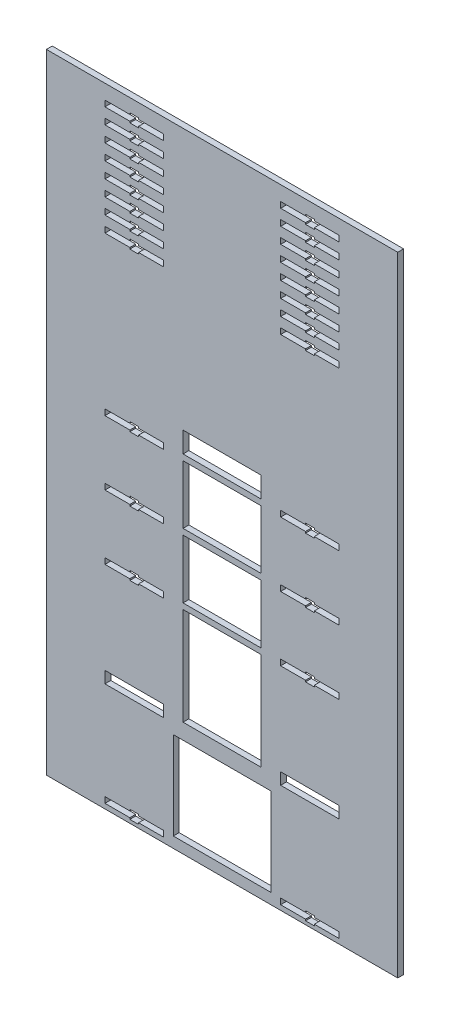
SolidWorks part; units mm, degrees
ref_plane "Front Plane" through (0, 0, 0) normal (0, 0, 1) x (1, 0, 0)
ref_plane "Top Plane" through (0, 0, 0) normal (0, 1, 0) x (1, 0, 0)
ref_plane "Right Plane" through (0, 0, 0) normal (1, 0, 0) x (0, 0, -1)
sketch "Sketch1" plane through (0, 0, 0) normal (0, 0, 1) x (1, 0, 0)
  line L0 (180, -180) -> (0, -180)
  line L1 (0, -180) -> (0, 142)
  line L2 (180, 142) -> (180, -180)
  line L3 (0, 142) -> (180, 142)
  line L4 (30, -174.5) -> (30, -177.5)
  line L5 (42.75, -174.5) -> (30, -174.5)
  line L6 (30, -177.5) -> (42.75, -177.5)
  line L7 (42.75, -173.75) -> (42.75, -174.5)
  line L8 (42.75, -177.5) -> (42.75, -178.25)
  line L9 (47.25, -173.75) -> (42.75, -173.75)
  line L10 (42.75, -178.25) -> (47.25, -178.25)
  line L11 (47.25, -174.5) -> (47.25, -173.75)
  line L12 (47.25, -178.25) -> (47.25, -177.5)
  line L13 (60, -174.5) -> (47.25, -174.5)
  line L14 (47.25, -177.5) -> (60, -177.5)
  line L15 (60, -177.5) -> (60, -174.5)
  line L16 (30, -121.5) -> (30, -124.5)
  line L17 (42.75, -121.5) -> (30, -121.5)
  line L18 (30, -124.5) -> (42.75, -124.5)
  line L19 (42.75, -120.75) -> (42.75, -121.5)
  line L20 (42.75, -124.5) -> (42.75, -125.25)
  line L21 (47.25, -120.75) -> (42.75, -120.75)
  line L22 (42.75, -125.25) -> (47.25, -125.25)
  line L23 (47.25, -121.5) -> (47.25, -120.75)
  line L24 (47.25, -125.25) -> (47.25, -124.5)
  line L25 (60, -121.5) -> (47.25, -121.5)
  line L26 (47.25, -124.5) -> (60, -124.5)
  line L27 (60, -124.5) -> (60, -121.5)
  line L28 (30, -68.5) -> (30, -71.5)
  line L29 (42.75, -68.5) -> (30, -68.5)
  line L30 (30, -71.5) -> (42.75, -71.5)
  line L31 (42.75, -67.75) -> (42.75, -68.5)
  line L32 (42.75, -71.5) -> (42.75, -72.25)
  line L33 (47.25, -67.75) -> (42.75, -67.75)
  line L34 (42.75, -72.25) -> (47.25, -72.25)
  line L35 (47.25, -68.5) -> (47.25, -67.75)
  line L36 (47.25, -72.25) -> (47.25, -71.5)
  line L37 (60, -68.5) -> (47.25, -68.5)
  line L38 (47.25, -71.5) -> (60, -71.5)
  line L39 (60, -71.5) -> (60, -68.5)
  line L40 (30, -35.5) -> (30, -38.5)
  line L41 (42.75, -35.5) -> (30, -35.5)
  line L42 (30, -38.5) -> (42.75, -38.5)
  line L43 (42.75, -34.75) -> (42.75, -35.5)
  line L44 (42.75, -38.5) -> (42.75, -39.25)
  line L45 (47.25, -34.75) -> (42.75, -34.75)
  line L46 (42.75, -39.25) -> (47.25, -39.25)
  line L47 (47.25, -35.5) -> (47.25, -34.75)
  line L48 (47.25, -39.25) -> (47.25, -38.5)
  line L49 (60, -35.5) -> (47.25, -35.5)
  line L50 (47.25, -38.5) -> (60, -38.5)
  line L51 (60, -38.5) -> (60, -35.5)
  line L52 (110, -5.5) -> (70, -5.5)
  line L53 (70, -5.5) -> (70, -135.5)
  line L54 (110, -135.5) -> (110, -5.5)
  line L55 (70, -135.5) -> (110, -135.5)
  line L56 (72.5, -174.5) -> (107.5, -174.5)
  line L57 (72.5, -147.5) -> (72.5, -174.5)
  line L58 (107.5, -174.5) -> (107.5, -147.5)
  line L59 (107.5, -147.5) -> (72.5, -147.5)
  line L60 (120, -174.5) -> (120, -177.5)
  line L61 (132.75, -174.5) -> (120, -174.5)
  line L62 (120, -177.5) -> (132.75, -177.5)
  line L63 (132.75, -173.75) -> (132.75, -174.5)
  line L64 (132.75, -177.5) -> (132.75, -178.25)
  line L65 (137.25, -173.75) -> (132.75, -173.75)
  line L66 (132.75, -178.25) -> (137.25, -178.25)
  line L67 (137.25, -174.5) -> (137.25, -173.75)
  line L68 (137.25, -178.25) -> (137.25, -177.5)
  line L69 (150, -174.5) -> (137.25, -174.5)
  line L70 (137.25, -177.5) -> (150, -177.5)
  line L71 (150, -177.5) -> (150, -174.5)
  line L72 (150, -121.5) -> (137.25, -121.5)
  line L73 (150, -124.5) -> (150, -121.5)
  line L74 (137.25, -121.5) -> (137.25, -120.75)
  line L75 (137.25, -124.5) -> (150, -124.5)
  line L76 (137.25, -120.75) -> (132.75, -120.75)
  line L77 (137.25, -125.25) -> (137.25, -124.5)
  line L78 (132.75, -120.75) -> (132.75, -121.5)
  line L79 (132.75, -125.25) -> (137.25, -125.25)
  line L80 (132.75, -121.5) -> (120, -121.5)
  line L81 (132.75, -124.5) -> (132.75, -125.25)
  line L82 (120, -121.5) -> (120, -124.5)
  line L83 (120, -124.5) -> (132.75, -124.5)
  line L84 (150, -68.5) -> (137.25, -68.5)
  line L85 (150, -71.5) -> (150, -68.5)
  line L86 (137.25, -68.5) -> (137.25, -67.75)
  line L87 (137.25, -71.5) -> (150, -71.5)
  line L88 (137.25, -67.75) -> (132.75, -67.75)
  line L89 (137.25, -72.25) -> (137.25, -71.5)
  line L90 (132.75, -67.75) -> (132.75, -68.5)
  line L91 (132.75, -72.25) -> (137.25, -72.25)
  line L92 (132.75, -68.5) -> (120, -68.5)
  line L93 (132.75, -71.5) -> (132.75, -72.25)
  line L94 (120, -68.5) -> (120, -71.5)
  line L95 (120, -71.5) -> (132.75, -71.5)
  line L96 (150, -35.5) -> (137.25, -35.5)
  line L97 (150, -38.5) -> (150, -35.5)
  line L98 (137.25, -35.5) -> (137.25, -34.75)
  line L99 (137.25, -38.5) -> (150, -38.5)
  line L100 (137.25, -34.75) -> (132.75, -34.75)
  line L101 (137.25, -39.25) -> (137.25, -38.5)
  line L102 (132.75, -34.75) -> (132.75, -35.5)
  line L103 (132.75, -39.25) -> (137.25, -39.25)
  line L104 (132.75, -35.5) -> (120, -35.5)
  line L105 (132.75, -38.5) -> (132.75, -39.25)
  line L106 (120, -35.5) -> (120, -38.5)
  line L107 (120, -38.5) -> (132.75, -38.5)
  line L108 (30, -2.5) -> (30, -5.5)
  line L109 (42.75, -2.5) -> (30, -2.5)
  line L110 (30, -5.5) -> (42.75, -5.5)
  line L111 (42.75, -1.75) -> (42.75, -2.5)
  line L112 (42.75, -5.5) -> (42.75, -6.25)
  line L113 (47.25, -1.75) -> (42.75, -1.75)
  line L114 (42.75, -6.25) -> (47.25, -6.25)
  line L115 (47.25, -2.5) -> (47.25, -1.75)
  line L116 (47.25, -6.25) -> (47.25, -5.5)
  line L117 (60, -2.5) -> (47.25, -2.5)
  line L118 (47.25, -5.5) -> (60, -5.5)
  line L119 (60, -5.5) -> (60, -2.5)
  line L120 (60, 75.5) -> (60, 78.5)
  line L121 (47.25, 75.5) -> (60, 75.5)
  line L122 (60, 78.5) -> (47.25, 78.5)
  line L123 (47.25, 74.75) -> (47.25, 75.5)
  line L124 (47.25, 78.5) -> (47.25, 79.25)
  line L125 (42.75, 74.75) -> (47.25, 74.75)
  line L126 (47.25, 79.25) -> (42.75, 79.25)
  line L127 (42.75, 75.5) -> (42.75, 74.75)
  line L128 (42.75, 79.25) -> (42.75, 78.5)
  line L129 (30, 75.5) -> (42.75, 75.5)
  line L130 (42.75, 78.5) -> (30, 78.5)
  line L131 (30, 78.5) -> (30, 75.5)
  line L132 (60, 83.5) -> (60, 86.5)
  line L133 (47.25, 83.5) -> (60, 83.5)
  line L134 (60, 86.5) -> (47.25, 86.5)
  line L135 (47.25, 82.75) -> (47.25, 83.5)
  line L136 (47.25, 86.5) -> (47.25, 87.25)
  line L137 (42.75, 82.75) -> (47.25, 82.75)
  line L138 (47.25, 87.25) -> (42.75, 87.25)
  line L139 (42.75, 83.5) -> (42.75, 82.75)
  line L140 (42.75, 87.25) -> (42.75, 86.5)
  line L141 (30, 83.5) -> (42.75, 83.5)
  line L142 (42.75, 86.5) -> (30, 86.5)
  line L143 (30, 86.5) -> (30, 83.5)
  line L144 (60, 91.5) -> (60, 94.5)
  line L145 (47.25, 91.5) -> (60, 91.5)
  line L146 (60, 94.5) -> (47.25, 94.5)
  line L147 (47.25, 90.75) -> (47.25, 91.5)
  line L148 (47.25, 94.5) -> (47.25, 95.25)
  line L149 (42.75, 90.75) -> (47.25, 90.75)
  line L150 (47.25, 95.25) -> (42.75, 95.25)
  line L151 (42.75, 91.5) -> (42.75, 90.75)
  line L152 (42.75, 95.25) -> (42.75, 94.5)
  line L153 (30, 91.5) -> (42.75, 91.5)
  line L154 (42.75, 94.5) -> (30, 94.5)
  line L155 (30, 94.5) -> (30, 91.5)
  line L156 (60, 99.5) -> (60, 102.5)
  line L157 (47.25, 99.5) -> (60, 99.5)
  line L158 (60, 102.5) -> (47.25, 102.5)
  line L159 (47.25, 98.75) -> (47.25, 99.5)
  line L160 (47.25, 102.5) -> (47.25, 103.25)
  line L161 (42.75, 98.75) -> (47.25, 98.75)
  line L162 (47.25, 103.25) -> (42.75, 103.25)
  line L163 (42.75, 99.5) -> (42.75, 98.75)
  line L164 (42.75, 103.25) -> (42.75, 102.5)
  line L165 (30, 99.5) -> (42.75, 99.5)
  line L166 (42.75, 102.5) -> (30, 102.5)
  line L167 (30, 102.5) -> (30, 99.5)
  line L168 (60, 107.5) -> (60, 110.5)
  line L169 (47.25, 107.5) -> (60, 107.5)
  line L170 (60, 110.5) -> (47.25, 110.5)
  line L171 (47.25, 106.75) -> (47.25, 107.5)
  line L172 (47.25, 110.5) -> (47.25, 111.25)
  line L173 (42.75, 106.75) -> (47.25, 106.75)
  line L174 (47.25, 111.25) -> (42.75, 111.25)
  line L175 (42.75, 107.5) -> (42.75, 106.75)
  line L176 (42.75, 111.25) -> (42.75, 110.5)
  line L177 (30, 107.5) -> (42.75, 107.5)
  line L178 (42.75, 110.5) -> (30, 110.5)
  line L179 (30, 110.5) -> (30, 107.5)
  line L180 (60, 115.5) -> (60, 118.5)
  line L181 (47.25, 115.5) -> (60, 115.5)
  line L182 (60, 118.5) -> (47.25, 118.5)
  line L183 (47.25, 114.75) -> (47.25, 115.5)
  line L184 (47.25, 118.5) -> (47.25, 119.25)
  line L185 (42.75, 114.75) -> (47.25, 114.75)
  line L186 (47.25, 119.25) -> (42.75, 119.25)
  line L187 (42.75, 115.5) -> (42.75, 114.75)
  line L188 (42.75, 119.25) -> (42.75, 118.5)
  line L189 (30, 115.5) -> (42.75, 115.5)
  line L190 (42.75, 118.5) -> (30, 118.5)
  line L191 (30, 118.5) -> (30, 115.5)
  line L192 (60, 123.5) -> (60, 126.5)
  line L193 (47.25, 123.5) -> (60, 123.5)
  line L194 (60, 126.5) -> (47.25, 126.5)
  line L195 (47.25, 122.75) -> (47.25, 123.5)
  line L196 (47.25, 126.5) -> (47.25, 127.25)
  line L197 (42.75, 122.75) -> (47.25, 122.75)
  line L198 (47.25, 127.25) -> (42.75, 127.25)
  line L199 (42.75, 123.5) -> (42.75, 122.75)
  line L200 (42.75, 127.25) -> (42.75, 126.5)
  line L201 (30, 123.5) -> (42.75, 123.5)
  line L202 (42.75, 126.5) -> (30, 126.5)
  line L203 (30, 126.5) -> (30, 123.5)
  line L204 (60, 131.5) -> (60, 134.5)
  line L205 (47.25, 131.5) -> (60, 131.5)
  line L206 (60, 134.5) -> (47.25, 134.5)
  line L207 (47.25, 130.75) -> (47.25, 131.5)
  line L208 (47.25, 134.5) -> (47.25, 135.25)
  line L209 (42.75, 130.75) -> (47.25, 130.75)
  line L210 (47.25, 135.25) -> (42.75, 135.25)
  line L211 (42.75, 131.5) -> (42.75, 130.75)
  line L212 (42.75, 135.25) -> (42.75, 134.5)
  line L213 (30, 131.5) -> (42.75, 131.5)
  line L214 (42.75, 134.5) -> (30, 134.5)
  line L215 (30, 134.5) -> (30, 131.5)
  line L216 (150, -2.5) -> (137.25, -2.5)
  line L217 (137.25, -2.5) -> (137.25, -1.75)
  line L218 (137.25, -1.75) -> (132.75, -1.75)
  line L219 (132.75, -1.75) -> (132.75, -2.5)
  line L220 (132.75, -2.5) -> (120, -2.5)
  line L221 (120, -2.5) -> (120, -5.5)
  line L222 (120, -5.5) -> (132.75, -5.5)
  line L223 (132.75, -5.5) -> (132.75, -6.25)
  line L224 (132.75, -6.25) -> (137.25, -6.25)
  line L225 (137.25, -6.25) -> (137.25, -5.5)
  line L226 (137.25, -5.5) -> (150, -5.5)
  line L227 (150, -5.5) -> (150, -2.5)
  line L228 (150, 75.5) -> (150, 78.5)
  line L229 (137.25, 75.5) -> (150, 75.5)
  line L230 (150, 78.5) -> (137.25, 78.5)
  line L231 (137.25, 74.75) -> (137.25, 75.5)
  line L232 (137.25, 78.5) -> (137.25, 79.25)
  line L233 (132.75, 74.75) -> (137.25, 74.75)
  line L234 (137.25, 79.25) -> (132.75, 79.25)
  line L235 (132.75, 75.5) -> (132.75, 74.75)
  line L236 (132.75, 79.25) -> (132.75, 78.5)
  line L237 (120, 75.5) -> (132.75, 75.5)
  line L238 (132.75, 78.5) -> (120, 78.5)
  line L239 (120, 78.5) -> (120, 75.5)
  line L240 (150, 83.5) -> (150, 86.5)
  line L241 (137.25, 83.5) -> (150, 83.5)
  line L242 (150, 86.5) -> (137.25, 86.5)
  line L243 (137.25, 82.75) -> (137.25, 83.5)
  line L244 (137.25, 86.5) -> (137.25, 87.25)
  line L245 (132.75, 82.75) -> (137.25, 82.75)
  line L246 (137.25, 87.25) -> (132.75, 87.25)
  line L247 (132.75, 83.5) -> (132.75, 82.75)
  line L248 (132.75, 87.25) -> (132.75, 86.5)
  line L249 (120, 83.5) -> (132.75, 83.5)
  line L250 (132.75, 86.5) -> (120, 86.5)
  line L251 (120, 86.5) -> (120, 83.5)
  line L252 (150, 91.5) -> (150, 94.5)
  line L253 (137.25, 91.5) -> (150, 91.5)
  line L254 (150, 94.5) -> (137.25, 94.5)
  line L255 (137.25, 90.75) -> (137.25, 91.5)
  line L256 (137.25, 94.5) -> (137.25, 95.25)
  line L257 (132.75, 90.75) -> (137.25, 90.75)
  line L258 (137.25, 95.25) -> (132.75, 95.25)
  line L259 (132.75, 91.5) -> (132.75, 90.75)
  line L260 (132.75, 95.25) -> (132.75, 94.5)
  line L261 (120, 91.5) -> (132.75, 91.5)
  line L262 (132.75, 94.5) -> (120, 94.5)
  line L263 (120, 94.5) -> (120, 91.5)
  line L264 (150, 99.5) -> (150, 102.5)
  line L265 (137.25, 99.5) -> (150, 99.5)
  line L266 (150, 102.5) -> (137.25, 102.5)
  line L267 (137.25, 98.75) -> (137.25, 99.5)
  line L268 (137.25, 102.5) -> (137.25, 103.25)
  line L269 (132.75, 98.75) -> (137.25, 98.75)
  line L270 (137.25, 103.25) -> (132.75, 103.25)
  line L271 (132.75, 99.5) -> (132.75, 98.75)
  line L272 (132.75, 103.25) -> (132.75, 102.5)
  line L273 (120, 99.5) -> (132.75, 99.5)
  line L274 (132.75, 102.5) -> (120, 102.5)
  line L275 (120, 102.5) -> (120, 99.5)
  line L276 (150, 107.5) -> (150, 110.5)
  line L277 (137.25, 107.5) -> (150, 107.5)
  line L278 (150, 110.5) -> (137.25, 110.5)
  line L279 (137.25, 106.75) -> (137.25, 107.5)
  line L280 (137.25, 110.5) -> (137.25, 111.25)
  line L281 (132.75, 106.75) -> (137.25, 106.75)
  line L282 (137.25, 111.25) -> (132.75, 111.25)
  line L283 (132.75, 107.5) -> (132.75, 106.75)
  line L284 (132.75, 111.25) -> (132.75, 110.5)
  line L285 (120, 107.5) -> (132.75, 107.5)
  line L286 (132.75, 110.5) -> (120, 110.5)
  line L287 (120, 110.5) -> (120, 107.5)
  line L288 (150, 115.5) -> (150, 118.5)
  line L289 (137.25, 115.5) -> (150, 115.5)
  line L290 (150, 118.5) -> (137.25, 118.5)
  line L291 (137.25, 114.75) -> (137.25, 115.5)
  line L292 (137.25, 118.5) -> (137.25, 119.25)
  line L293 (132.75, 114.75) -> (137.25, 114.75)
  line L294 (137.25, 119.25) -> (132.75, 119.25)
  line L295 (132.75, 115.5) -> (132.75, 114.75)
  line L296 (132.75, 119.25) -> (132.75, 118.5)
  line L297 (120, 115.5) -> (132.75, 115.5)
  line L298 (132.75, 118.5) -> (120, 118.5)
  line L299 (120, 118.5) -> (120, 115.5)
  line L300 (150, 123.5) -> (150, 126.5)
  line L301 (137.25, 123.5) -> (150, 123.5)
  line L302 (150, 126.5) -> (137.25, 126.5)
  line L303 (137.25, 122.75) -> (137.25, 123.5)
  line L304 (137.25, 126.5) -> (137.25, 127.25)
  line L305 (132.75, 122.75) -> (137.25, 122.75)
  line L306 (137.25, 127.25) -> (132.75, 127.25)
  line L307 (132.75, 123.5) -> (132.75, 122.75)
  line L308 (132.75, 127.25) -> (132.75, 126.5)
  line L309 (120, 123.5) -> (132.75, 123.5)
  line L310 (132.75, 126.5) -> (120, 126.5)
  line L311 (120, 126.5) -> (120, 123.5)
  line L312 (150, 131.5) -> (150, 134.5)
  line L313 (137.25, 131.5) -> (150, 131.5)
  line L314 (150, 134.5) -> (137.25, 134.5)
  line L315 (137.25, 130.75) -> (137.25, 131.5)
  line L316 (137.25, 134.5) -> (137.25, 135.25)
  line L317 (132.75, 130.75) -> (137.25, 130.75)
  line L318 (137.25, 135.25) -> (132.75, 135.25)
  line L319 (132.75, 131.5) -> (132.75, 130.75)
  line L320 (132.75, 135.25) -> (132.75, 134.5)
  line L321 (120, 131.5) -> (132.75, 131.5)
  line L322 (132.75, 134.5) -> (120, 134.5)
  line L323 (120, 134.5) -> (120, 131.5)
extrude "Plate_thickness_3mm" add sketch "Sketch1" along normal blind 3
sketch "Sketch2" plane through (0, 0, 3) normal (0, 0, 1) x (1, 0, 0)
  line L0 (70, -5.5) -> (110, -5.5)
  line L1 (70, -5.5) -> (70, 8.0917)
  line L2 (110, -5.5) -> (110, 8.0917)
  line L3 (70, 8.0917) -> (110, 8.0917)
extrude "Cut-Extrude1" cut sketch "Sketch2" against normal blind 15.24
sketch "草图1" plane through (0, 0, 3) normal (0, 0, 1) x (1, 0, 0)
  line L0 (90, -147.5) -> (90, -174.5)
  line L1 (107.5, -147.5) -> (72.5, -147.5) construction
  line L2 (72.5, -174.5) -> (107.5, -174.5) construction
  line L3 (72.5, -161) -> (107.5, -161)
  line L4 (72.5, -147.5) -> (72.5, -174.5) construction
  line L5 (107.5, -174.5) -> (107.5, -147.5) construction
  line L6 (47.25, -124.5) -> (60, -124.5) construction
  line L12 (65, -174.5) -> (115, -174.5)
  line L13 (60, -174.5) -> (47.25, -174.5) construction
  line L14 (65, -174.5) -> (65, -129.5)
  line L15 (65, -129.5) -> (115, -129.5)
  line L16 (115, -174.5) -> (115, -129.5)
  point P12 (90, -161)
  dimension "D1" = 50
  dimension "D2" = 50
  dimension "D3" = 45
  dimension "D4" = 25
extrude "切除-拉伸1" cut sketch "草图1" against normal through all contours L12 L16 L15 L14 region at (65.6727, -152, 3)
sketch "草图2" plane through (0, 0, 3) normal (0, 0, 1) x (1, 0, 0)
  line L0 (110, -129.5) -> (110, 8.0917) construction
  line L1 (70, -129.5) -> (110, -129.5)
  line L2 (70, -129.5) -> (70, -121.5)
  line L3 (70, -121.5) -> (110, -121.5)
  line L4 (110, -129.5) -> (110, -121.5)
  line L5 (70, 8.0917) -> (70, -129.5) construction
  line L6 (70, -71.5) -> (110, -71.5)
  line L7 (70, -71.5) -> (70, -68.5899)
  line L8 (70, -68.5899) -> (110, -68.5899)
  line L9 (110, -71.5) -> (110, -68.5899)
  line L10 (60, -35.5) -> (70, -35.5)
  line L12 (70, -35.5) -> (110, -35.5)
  line L13 (70, -35.5) -> (70, -38.5)
  line L14 (70, -38.5) -> (110, -38.5)
  line L15 (110, -35.5) -> (110, -38.5)
  line L16 (70, -2.5) -> (110, -2.5)
  line L17 (70, -2.5) -> (70, -5.5)
  line L18 (70, -5.5) -> (110, -5.5)
  line L19 (110, -2.5) -> (110, -5.5)
extrude "凸台-拉伸1" add sketch "草图2" against normal up to surface (3 mm away) contours L19 L16 L17 L18 | L15 L12 L13 L14 | L6 L9 L8 L7 | L1 L4 L3 L2 region at (90, -125.5, 3) region at (90, -70.045, 3) region at (90, -37, 3) region at (90, -4, 3) up to face at (90, -19, 0)
sketch "草图3" plane through (0, 0, 3) normal (0, 0, 1) x (1, 0, 0)
  line L0 (90, -180) -> (90, -111.1759)
  line L1 (30, -124.5) -> (60, -124.5)
  line L2 (30, -124.5) -> (30, -118.5)
  line L3 (30, -118.5) -> (60, -118.5)
  line L4 (60, -124.5) -> (60, -118.5)
  line L5 (42.75, -125.25) -> (47.25, -125.25)
  line L6 (42.75, -125.25) -> (42.75, -124.5)
  line L7 (42.75, -124.5) -> (47.25, -124.5)
  line L8 (47.25, -125.25) -> (47.25, -124.5)
  line L9 (0, -180) -> (180, -180) construction
  line L10 (137.25, -124.5) -> (132.75, -124.5)
  line L11 (132.75, -125.25) -> (132.75, -124.5)
  line L12 (137.25, -125.25) -> (132.75, -125.25)
  line L13 (137.25, -125.25) -> (137.25, -124.5)
  line L14 (150, -118.5) -> (120, -118.5)
  line L15 (120, -124.5) -> (120, -118.5)
  line L16 (150, -124.5) -> (120, -124.5)
  line L17 (150, -124.5) -> (150, -118.5)
  dimension "D1" = 6
  dimension "D2" = 30
extrude "切除-拉伸2" cut sketch "草图3" against normal through all contours L1 L4 L3 L2 | L16 L17 L14 L15 L10 region at (45, -121.5, 3) region at (135, -121.5, 3)
extrude "凸台-拉伸2" add sketch "草图3<3>" against normal up to surface (3 mm away) contours L5 L8 L1 L6 | L12 L13 L10 L11 region at (45, -124.875, 3) region at (135, -124.875, 3) up to face at (90, -20.5, 0)
sketch "草图3<3>" plane through (0, 0, 3) normal (0, 0, 1) x (1, 0, 0) same geometry as "草图3"
